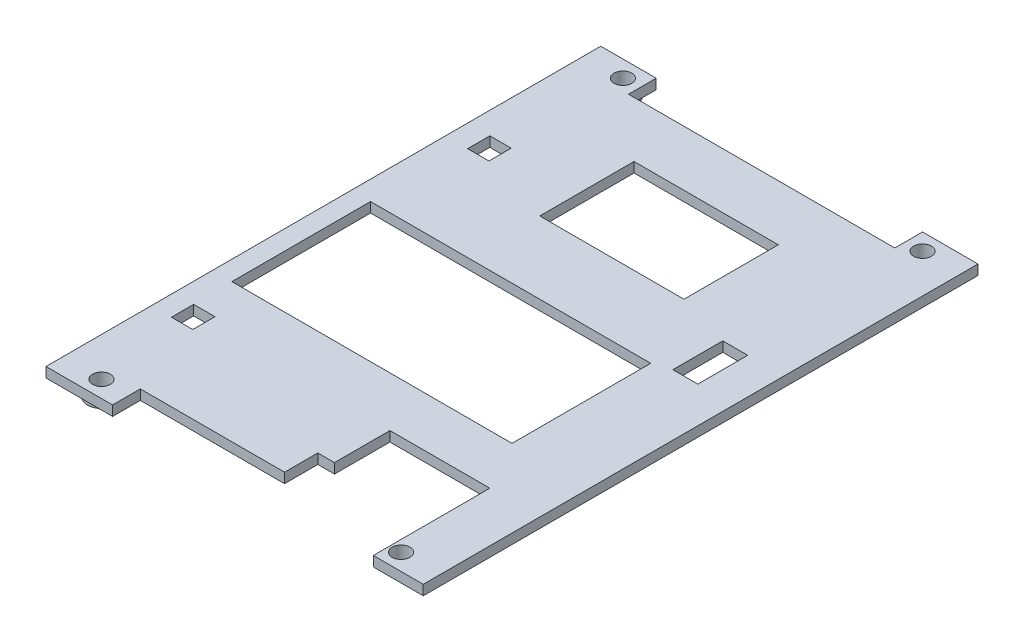
SolidWorks part; units mm, degrees
ref_plane "前视基准面" through (0, 0, 0) normal (0, 0, 1) x (1, 0, 0)
ref_plane "上视基准面" through (0, 0, 0) normal (0, 1, 0) x (1, 0, 0)
ref_plane "右视基准面" through (0, 0, 0) normal (1, 0, 0) x (0, 0, -1)
sketch "草图1" plane through (0, 0, 0) normal (0, 1, 0) x (1, 0, 0)
  line L1 (0, 0) -> (68, 0)
  line L2 (0, 0) -> (0, -100)
  line L3 (0, -100) -> (68, -100)
  line L4 (68, 0) -> (68, -100)
  dimension "D1" = 68
  dimension "D2" = 100
extrude "凸台-拉伸1" add sketch "草图1" along normal blind 1.8
sketch "草图2" plane through (0, 1.8, 0) normal (0, 1, 0) x (1, 0, 0)
  line L0 (68, 0) -> (0, 0) construction
  line L1 (10, 0) -> (58, 0)
  line L2 (10, 0) -> (10, -5)
  line L3 (10, -5) -> (58, -5)
  line L4 (58, 0) -> (58, -5)
  line L5 (0, 0) -> (0, -100) construction
  line L6 (21, -15) -> (47, -15)
  line L7 (21, -15) -> (21, -32)
  line L8 (21, -32) -> (47, -32)
  line L9 (47, -15) -> (47, -32)
  line L10 (68, -100) -> (68, 0) construction
  line L12 (4, -24) -> (7.8464, -24)
  line L13 (4, -24) -> (4, -28)
  line L14 (4, -28) -> (7.8464, -28)
  line L15 (7.8464, -24) -> (7.8464, -28)
  line L16 (3.6119, -77) -> (7.4582, -77)
  line L17 (3.5, -45) -> (54, -45)
  line L18 (3.5, -45) -> (3.5, -70)
  line L19 (3.5, -70) -> (54, -70)
  line L20 (54, -45) -> (54, -70)
  line L21 (3.6119, -77) -> (3.6119, -81)
  line L22 (3.6119, -81) -> (7.4582, -81)
  line L23 (7.4582, -77) -> (7.4582, -81)
  line L24 (0, -100) -> (68, -100) construction
  line L26 (12, -100) -> (36, -100)
  line L27 (12, -100) -> (12, -95)
  line L28 (12, -95) -> (36, -95)
  line L29 (36, -100) -> (36, -95)
  line L30 (41, -100) -> (59, -100)
  line L31 (41, -100) -> (41, -83.2083)
  line L32 (41, -83.2083) -> (59, -83.2083)
  line L33 (59, -100) -> (59, -83.2083)
  line L34 (57, -35) -> (61.5, -35)
  line L35 (57, -35) -> (57, -44)
  line L36 (57, -44) -> (61.5, -44)
  line L37 (61.5, -35) -> (61.5, -44)
  dimension "D1" = 5
  dimension "D2" = 10
  dimension "D3" = 10
  dimension "D4" = 15
  dimension "D5" = 21
  dimension "D6" = 21
  dimension "D7" = 32
  dimension "D8" = 24
  dimension "D9" = 4
  dimension "D10" = 4
  dimension "D11" = 25
  dimension "D12" = 3.5
  dimension "D13" = 14
  dimension "D14" = 19
  dimension "D15" = 45
  dimension "D16" = 30
  dimension "D17" = 12
  dimension "D18" = 36
  dimension "D19" = 5
  dimension "D20" = 9
  dimension "D21" = 27
  dimension "D22" = 6.5
  dimension "D23" = 11
  dimension "D24" = 35
  dimension "D25" = 9
extrude "切除-拉伸1" cut sketch "草图2" against normal blind 1.8
sketch "草图4" plane through (0, 0, 0) normal (0, -1, 0) x (1, 0, 0)
  circle A0 centre (7, 97) radius 1.4
  circle A1 centre (7, 97) radius 2.5
  circle A2 centre (61, 97) radius 1.4
  circle A3 centre (61, 97) radius 2
  circle A4 centre (61, 3) radius 1.4
  circle A5 centre (61, 3) radius 2.5
  circle A6 centre (7, 3) radius 1.4
  circle A7 centre (7, 3) radius 2.5
extrude "凸台-拉伸3" add sketch "草图4" along normal blind 1
sketch "草图6" plane through (0, 0, 0) normal (0, -1, 0) x (1, 0, 0)
  circle A0 centre (7, 97) radius 1.4
  circle A1 centre (61, 97) radius 1.4
  circle A2 centre (61, 3) radius 1.4
  circle A3 centre (7, 3) radius 1.4
extrude "切除-拉伸3" cut sketch "草图6" against normal blind 14
sketch "草图8" plane through (0, 1.8, 0) normal (0, 1, 0) x (1, 0, 0)
  line L1 (36, -95) -> (41, -95)
  line L2 (36, -95) -> (36, -100)
  line L3 (36, -100) -> (41, -100)
  line L4 (41, -95) -> (41, -100)
  line L5 (36, -100) -> (36, -95) construction
  line L6 (59, -100) -> (68, -100) construction
  line L7 (41, -83.2083) -> (59, -83.2083)
  line L8 (41, -83.2083) -> (41, -79)
  line L9 (41, -79) -> (59, -79)
  line L10 (59, -83.2083) -> (59, -79)
  line L11 (59, -100) -> (59, -83.2083) construction
  line L12 (41, -83.2083) -> (41, -100) construction
  dimension "D2" = 21
extrude "切除-拉伸4" cut sketch "草图8" against normal blind 10
sketch "草图9" plane through (0, 1.8, 0) normal (0, 1, 0) x (1, 0, 0)
  circle A0 centre (7, -3) radius 1.6
  circle A1 centre (61, -3) radius 1.6
  circle A2 centre (61, -97) radius 1.6
  circle A3 centre (7, -97) radius 1.6
extrude "切除-拉伸5" cut sketch "草图9" against normal blind 10
sketch "草图10" plane through (0, 0, 0) normal (0, -1, 0) x (1, 0, 0)
  line L1 (41, 95) -> (38, 95)
  line L2 (41, 95) -> (41, 89)
  line L3 (41, 89) -> (38, 89)
  line L4 (38, 95) -> (38, 89)
  dimension "D1" = 3
  dimension "D2" = 6
extrude "切除-拉伸6" cut sketch "草图10" against normal blind 10
